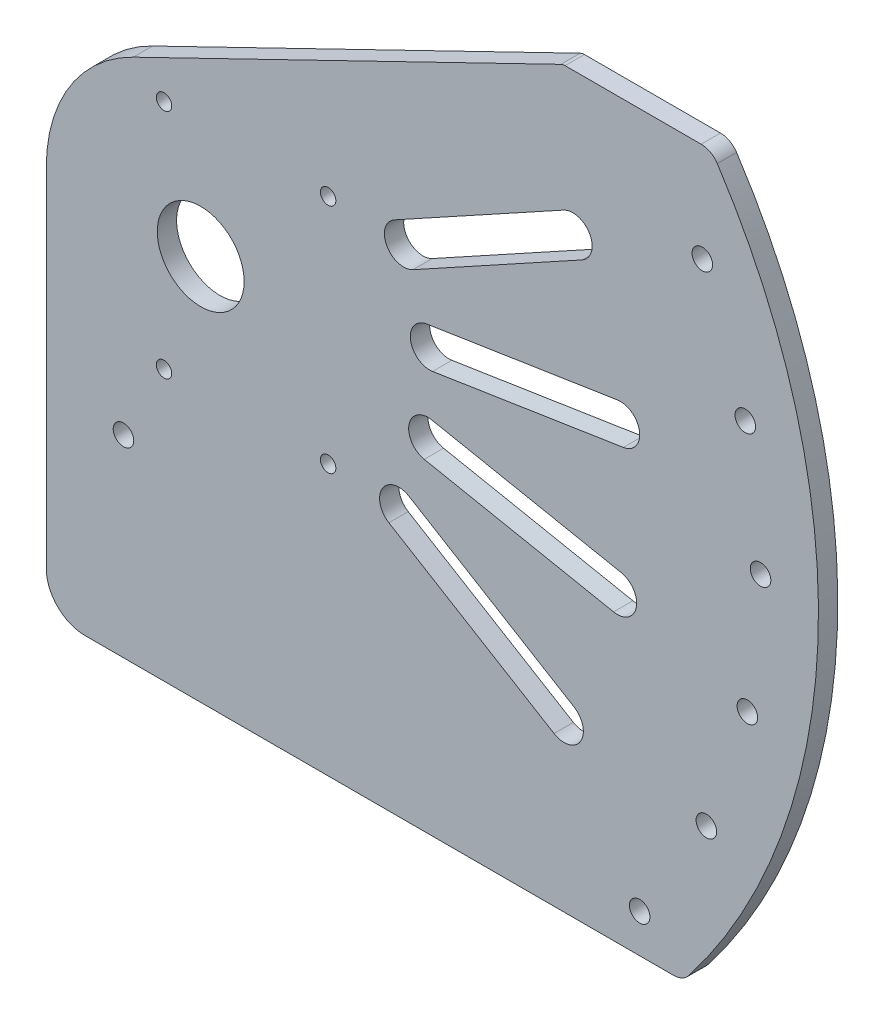
SolidWorks part; units mm, degrees
ref_plane "Front Plane" through (0, 0, 0) normal (0, 0, 1) x (1, 0, 0)
ref_plane "Top Plane" through (0, 0, 0) normal (0, 1, 0) x (1, 0, 0)
ref_plane "Right Plane" through (0, 0, 0) normal (1, 0, 0) x (0, 0, -1)
sketch "Sketch1" plane through (0, 0, 0) normal (0, 0, 1) x (1, 0, 0)
  line L1 (119.1366, 114.3) -> (164.6108, 114.3)
  line L2 (-50.8, 0) -> (-50.8, -114.3)
  line L3 (-38.1, -127) -> (155.5426, -127)
  line L8 (119.1366, 114.3) -> (-22.1838, 45.7003)
  line L12 (66.7662, 36.7249) -> (122.4047, 67.3289) construction
  line L13 (63.7058, 42.2887) -> (119.3443, 72.8927)
  line L14 (69.8266, 31.161) -> (125.4651, 61.765)
  line L16 (75.3003, 11.6747) -> (138.0506, 21.4036) construction
  line L17 (74.3275, 17.9497) -> (137.0777, 27.6786)
  line L18 (76.2732, 5.3997) -> (139.0235, 15.1286)
  line L20 (74.7522, -14.7836) -> (137.0456, -27.1033) construction
  line L21 (75.9841, -8.5543) -> (138.2776, -20.874)
  line L22 (73.5202, -21.013) -> (135.8136, -33.3326)
  line L24 (65.1878, -39.4588) -> (119.5109, -72.3411) construction
  line L25 (68.476, -34.0265) -> (122.7991, -66.9088)
  line L26 (61.8995, -44.8911) -> (116.2226, -77.7734)
  line L29 (36.6574, 35.1692) -> (119.1366, 114.3)
  line L35 (149.1104, -70.8808) -> (166.3251, -79.0426) construction
  line L37 (39.8301, -31.531) -> (144.384, -114.3) construction
  line L38 (32.4597, -39.0769) -> (105.4941, -127)
  circle A0 centre (0, 0) radius 14.2875
  circle A1 centre (0, 0) radius 50.8
  arc A2 (105.4941, -127) -> (119.1366, 114.3) centre (0, 0) ccw
  arc A3 (-50.8, -114.3) -> (-38.1, -127) centre (-38.1, -114.3) ccw
  arc A4 (160.5601, -124.5419) -> (169.9208, 111.4323) centre (0, 0) ccw
  arc A5 (133.35, -127) -> (142.263, -116.9294) centre (0, 0) ccw
  circle A6 centre (144.384, -114.3) radius 3.3782
  circle A7 centre (166.3251, -79.0426) radius 3.3782
  circle A8 centre (179.8084, -39.7654) radius 3.3782
  circle A9 centre (184.1483, 1.5342) radius 3.3782
  circle A10 centre (179.124, 42.7562) radius 3.3782
  circle A11 centre (164.9912, 81.8044) radius 3.3782
  arc A12 (167.7457, -75.9776) -> (179.0457, -43.0564) centre (0, 0) ccw
  arc A13 (146.4564, -111.6322) -> (164.8458, -82.0797) centre (0, 0) ccw
  arc A14 (180.5046, -36.4597) -> (184.1408, -1.844) centre (0, 0) ccw
  arc A15 (184.0845, 4.9118) -> (179.8721, 39.4619) centre (0, 0) ccw
  arc A16 (163.456, 84.8136) -> (144.384, 114.3) centre (0, 0) ccw
  arc A17 (178.3036, 46.0333) -> (166.4571, 78.7608) centre (0, 0) ccw
  arc A18 (169.9208, 111.4323) -> (164.6108, 114.3) centre (164.6108, 107.95) ccw
  arc A19 (160.5601, -124.5419) -> (155.5426, -127) centre (155.5426, -120.65) cw
  arc A20 (63.7058, 42.2887) -> (69.8266, 31.161) centre (66.7662, 36.7249) ccw
  arc A21 (125.4651, 61.765) -> (119.3443, 72.8927) centre (122.4047, 67.3289) ccw
  arc A22 (74.3275, 17.9497) -> (76.2732, 5.3997) centre (75.3003, 11.6747) ccw
  arc A23 (139.0235, 15.1286) -> (137.0777, 27.6786) centre (138.0506, 21.4036) ccw
  arc A24 (75.9841, -8.5543) -> (73.5202, -21.013) centre (74.7522, -14.7836) ccw
  arc A25 (135.8136, -33.3326) -> (138.2776, -20.874) centre (137.0456, -27.1033) ccw
  arc A26 (68.476, -34.0265) -> (61.8995, -44.8911) centre (65.1878, -39.4588) ccw
  arc A27 (116.2226, -77.7734) -> (122.7991, -66.9088) centre (119.5109, -72.3411) ccw
  circle A28 centre (-25.4, -63.5) radius 3.3782
  point P54 (94.5854, 52.0269)
  point P65 (106.6755, 16.5391)
  point P73 (105.8989, -20.9435)
  point P81 (92.3493, -55.9)
  dimension "D1" = 28.575
  dimension "D6" = 101.6
  dimension "D7" = 330.2
  dimension "D8" = 12.7
  dimension "D9" = 406.4
  dimension "D10" = 184.15
  dimension "D11" = 6.7564
  dimension "D15" = 6.35
  dimension "D19" = 6.35
  dimension "D14" = 63.5
  dimension "D5" = 6.7564
  dimension "D2" = 114.3
  dimension "D3" = 127
  dimension "D4" = 50.8
  dimension "D12" = 12.7
  dimension "D16" = 25.4
  dimension "D17" = 76.2
  dimension "D18" = 63.5
  dimension "D13" = 6
  dimension "D20" = 4
extrude "Boss-Extrude1" add sketch "Sketch1" along normal blind 6.35 contours L1 L2 L3 A2 A1 | A1 A0 | L3 A4 L1 A2 | A1 | A17 A10 A15 A9 A14 A8 A12 A7 A13 A6 A5 L3 A4 L1 A16 A11 | A2 L8 A1 | A1 L29 L8 | L38 | A1 L38 region at (50.6547, 68.5259, 0) region at (106.2086, -6.8125, 0) region at (131.7603, 111.7621, 0) region at (154.4974, 111.7879, 0) region at (8.6966, 48.5911, 0) region at (10.6193, -88.4607, 0)
fillet "Fillet1" radius 3.175 1 edges at (119.1366, 114.3, 3.175)
sketch "Sketch2" plane through (0, 0, 6.35) normal (0, 0, 1) x (1, 0, 0)
  line L0 (19.6773, 22.86) -> (19.6773, -22.86)
  line L1 (-24.7727, 50.8) -> (51.4273, 50.8)
  line L2 (-24.7727, 50.8) -> (-24.7727, -50.8)
  line L3 (-24.7727, -50.8) -> (51.4273, -50.8)
  line L4 (51.4273, 50.8) -> (51.4273, -50.8)
  line L5 (19.6773, 22.86) -> (0, 0)
  line L6 (0, 0) -> (19.6773, -22.86)
  circle A0 centre (19.6773, 22.86) radius 22.225
  circle A1 centre (19.6773, -22.86) radius 22.225
  circle A2 centre (-12.0727, 38.1) radius 2.54
  circle A3 centre (-12.0727, -38.1) radius 2.54
  circle A4 centre (41.9023, -38.1) radius 2.54
  circle A5 centre (41.9023, 38.1) radius 2.54
  point P4 (19.6773, 0)
  dimension "D7" = 50.8
  dimension "D8" = 44.45
  dimension "D4" = 44.45
  dimension "D12" = 5.08
  dimension "D13" = 5.08
  dimension "D16" = 5.08
  dimension "D17" = 5.08
  dimension "D1" = 0
  dimension "D2" = 45.72
  dimension "D3" = 30.1625
  dimension "D5" = 31.75
  dimension "D6" = 44.45
  dimension "D9" = 50.8
  dimension "D10" = 12.7
  dimension "D11" = 9.525
  dimension "D14" = 9.525
  dimension "D15" = 12.7
  dimension "D18" = 12.7
  dimension "D19" = 12.7
  dimension "D20" = 12.7
  dimension "D21" = 12.7
extrude "Cut-Extrude1" cut sketch "Sketch2" against normal up to surface (6.35 mm away) contours A2 | A5 | A4 | A3 up to face at (75.6332, 0.702, 0)
